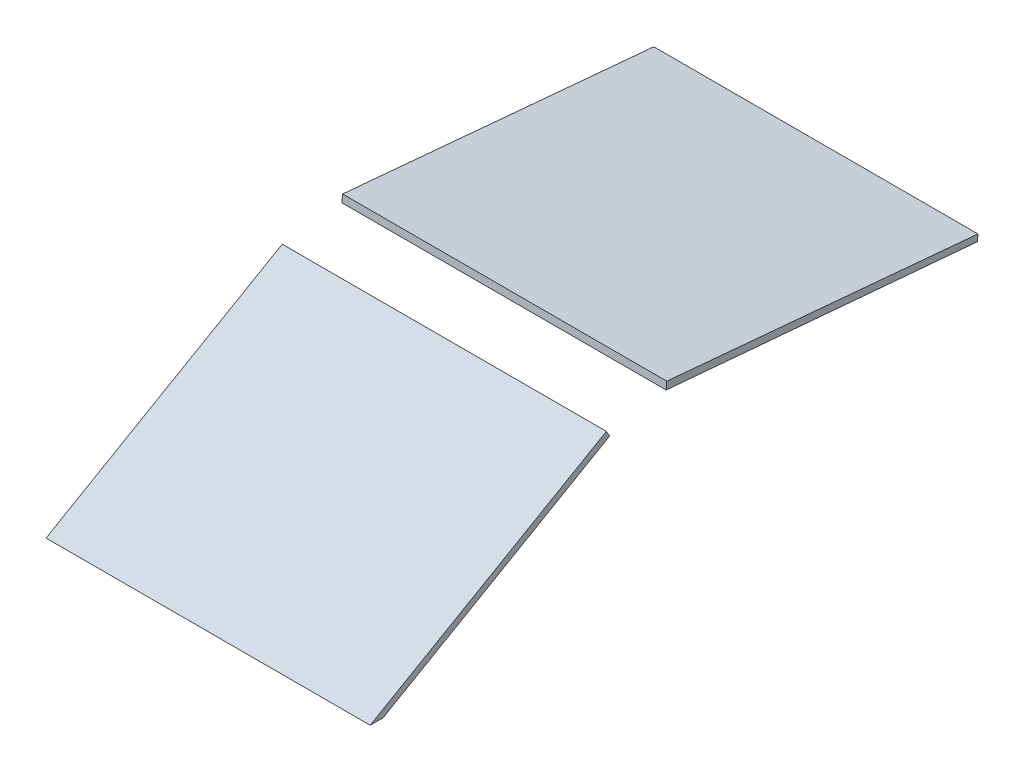
SolidWorks part; units mm, degrees
ref_plane "Front Plane" through (0, 0, 0) normal (0, 0, 1) x (1, 0, 0)
ref_plane "Top Plane" through (0, 0, 0) normal (0, 1, 0) x (1, 0, 0)
ref_plane "Right Plane" through (0, 0, 0) normal (1, 0, 0) x (0, 0, -1)
sketch "Sketch1" plane through (0, 0, 0) normal (1, 0, 0) x (0, 0, -1)
  line L0 (0, 0) -> (80186.3007, 0) construction
  line L1 (0, 0) -> (116.2899, 67.14)
  line L2 (116.2899, 67.14) -> (274.9638, 53.2578)
  line L3 (-6, 0) -> (0, 0)
  line L4 (116.2899, 67.14) -> (116.2899, 70.6041) construction
  line L5 (-6, 0) -> (116.2899, 70.6041)
  line L6 (274.9638, 53.2578) -> (275.2252, 56.2464)
  line L7 (275.2252, 56.2464) -> (116.2899, 70.6041)
  dimension "D1" = 134.28
  dimension "D2" = 30
  dimension "D3" = 145
  dimension "D4" = 159.28
  dimension "D5" = 3
  dimension "D6" = 3
extrude "Boss-Extrude1" add sketch "Sketch1" along normal blind 150
sketch "Sketch4" plane through (150, 0, 0) normal (1, 0, 0) x (0, 0, -1)
  line L0 (103.2995, 63.1041) -> (104.7995, 60.506)
  line L1 (116.2899, 70.6041) -> (-6, 0) construction
  line L2 (0, 0) -> (116.2899, 67.14) construction
  line L3 (103.2995, 63.1041) -> (116.2899, 70.6041)
  line L4 (116.2899, 70.6041) -> (131.2291, 69.2545)
  line L5 (275.2252, 56.2464) -> (116.2899, 70.6041) construction
  line L6 (131.2291, 69.2545) -> (130.932, 65.859)
  line L7 (116.2899, 67.14) -> (274.9638, 53.2578) construction
  line L8 (130.932, 65.859) -> (116.2899, 67.14)
  line L9 (116.2899, 67.14) -> (104.7995, 60.506)
  dimension "D1" = 15
  dimension "D2" = 15
extrude "Cut-Extrude1" cut sketch "Sketch4" against normal through all
